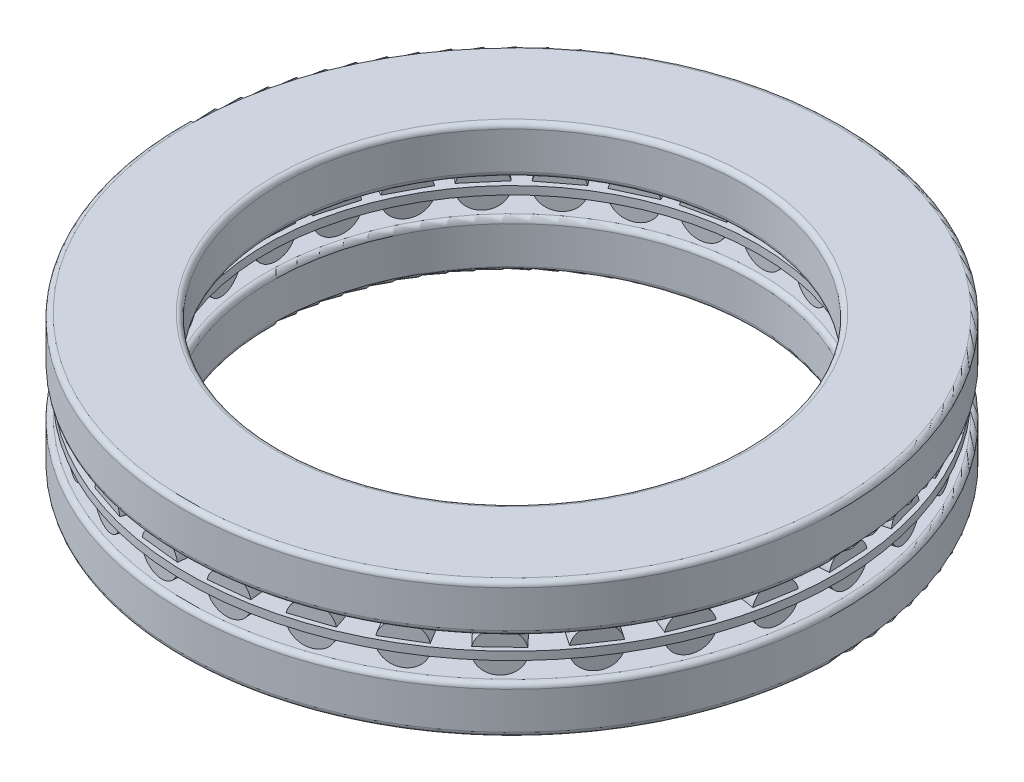
SolidWorks part; units mm, degrees
ref_plane "前视基准面" through (0, 0, 0) normal (0, 0, 1) x (1, 0, 0)
ref_plane "上视基准面" through (0, 0, 0) normal (0, 1, 0) x (1, 0, 0)
ref_plane "右视基准面" through (0, 0, 0) normal (1, 0, 0) x (0, 0, -1)
sketch "草图1" plane through (0, 0, 0) normal (1, 0, 0) x (0, 0, -1)
  line L0 (0, 40.2628) -> (0, 0) construction
  line L1 (0, 0) -> (70.6499, 0) construction
  line L2 (0, 0) -> (0, -0.6) construction
  line L3 (29.1, 2.8) -> (38.4, 2.8)
  line L4 (28.5, 2.2) -> (28.5, -2.2)
  line L5 (29.1, -2.8) -> (38.4, -2.8)
  line L6 (39, 2.2) -> (39, -2.2)
  line L7 (28.1, 13.2) -> (38.4, 13.2)
  line L8 (27.5, 12.6) -> (27.5, 8.2)
  line L9 (28.1, 7.6) -> (38.4, 7.6)
  line L10 (39, 12.6) -> (39, 8.2)
  line L11 (38.4, 5.2) -> (29.1, 5.2) construction
  line L12 (38.4, 5.68) -> (29.1, 5.68)
  line L13 (38.4, 5.68) -> (38.4, 4.72)
  line L14 (38.4, 4.72) -> (29.1, 4.72)
  line L15 (29.1, 5.68) -> (29.1, 4.72)
  arc A0 (38.4, -2.8) -> (39, -2.2) centre (38.4, -2.2) ccw
  arc A1 (38.4, 2.8) -> (39, 2.2) centre (38.4, 2.2) cw
  arc A2 (28.5, -2.2) -> (29.1, -2.8) centre (29.1, -2.2) ccw
  arc A3 (29.1, 2.8) -> (28.5, 2.2) centre (29.1, 2.2) ccw
  arc A4 (38.4, 13.2) -> (39, 12.6) centre (38.4, 12.6) cw
  arc A5 (38.4, 7.6) -> (39, 8.2) centre (38.4, 8.2) ccw
  arc A6 (27.5, 8.2) -> (28.1, 7.6) centre (28.1, 8.2) ccw
  arc A7 (28.1, 13.2) -> (27.5, 12.6) centre (28.1, 12.6) ccw
  dimension "D3" = 0.6
  dimension "D1" = 57
  dimension "T" = 16
  dimension "D" = 78
  dimension "D2" = 4.8
  dimension "(d1)" = 78
  dimension "(d)" = 55
  dimension "r" = 0.6
  dimension "D4" = 0.96
sketch "草图2" plane through (0, 0, 0) normal (1, 0, 0) x (0, 0, -1)
  line L0 (29.1, 2.8) -> (38.4, 2.8) construction
  line L1 (39, 2.2) -> (39, -2.2) construction
  line L2 (29.1, -2.8) -> (38.4, -2.8) construction
  line L3 (28.5, 2.2) -> (28.5, -2.2) construction
  line L4 (29.1, 2.8) -> (38.4, 2.8)
  line L5 (39, 2.2) -> (39, -2.2)
  line L6 (29.1, -2.8) -> (38.4, -2.8)
  line L7 (28.5, 2.2) -> (28.5, -2.2)
  line L8 (0, 0) -> (0, 14.9997) construction
  line L9 (0, 40.2628) -> (0, 0) construction
  arc A0 (39, 2.2) -> (38.4, 2.8) centre (38.4, 2.2) ccw construction
  arc A1 (38.4, -2.8) -> (39, -2.2) centre (38.4, -2.2) ccw construction
  arc A2 (28.5, -2.2) -> (29.1, -2.8) centre (29.1, -2.2) ccw construction
  arc A3 (29.1, 2.8) -> (28.5, 2.2) centre (29.1, 2.2) ccw construction
  arc A4 (39, 2.2) -> (38.4, 2.8) centre (38.4, 2.2) ccw
  arc A5 (38.4, -2.8) -> (39, -2.2) centre (38.4, -2.2) ccw
  arc A6 (28.5, -2.2) -> (29.1, -2.8) centre (29.1, -2.2) ccw
  arc A7 (29.1, 2.8) -> (28.5, 2.2) centre (29.1, 2.2) ccw
revolve "旋转1" add sketch "草图2" angle 360 mid plane about L8
sketch "草图3" plane through (0, 0, 0) normal (1, 0, 0) x (0, 0, -1)
  line L0 (28.1, 13.2) -> (38.4, 13.2) construction
  line L1 (39, 12.6) -> (39, 8.2) construction
  line L2 (28.1, 7.6) -> (38.4, 7.6) construction
  line L3 (27.5, 12.6) -> (27.5, 8.2) construction
  line L4 (28.1, 13.2) -> (38.4, 13.2)
  line L5 (39, 12.6) -> (39, 8.2)
  line L6 (28.1, 7.6) -> (38.4, 7.6)
  line L7 (27.5, 12.6) -> (27.5, 8.2)
  line L8 (0, 0) -> (0, 10.4732) construction
  line L9 (0, 40.2628) -> (0, 0) construction
  arc A0 (39, 12.6) -> (38.4, 13.2) centre (38.4, 12.6) ccw construction
  arc A1 (38.4, 7.6) -> (39, 8.2) centre (38.4, 8.2) ccw construction
  arc A2 (27.5, 8.2) -> (28.1, 7.6) centre (28.1, 8.2) ccw construction
  arc A3 (28.1, 13.2) -> (27.5, 12.6) centre (28.1, 12.6) ccw construction
  arc A4 (39, 12.6) -> (38.4, 13.2) centre (38.4, 12.6) ccw
  arc A5 (38.4, 7.6) -> (39, 8.2) centre (38.4, 8.2) ccw
  arc A6 (27.5, 8.2) -> (28.1, 7.6) centre (28.1, 8.2) ccw
  arc A7 (28.1, 13.2) -> (27.5, 12.6) centre (28.1, 12.6) ccw
revolve "旋转2" add sketch "草图3" angle 360 mid plane about L8
ref_plane "基准面1" through (0, 5.2, 0) normal (0, -1, 0) x (1, 0, 0)
sketch "草图7" plane through (0, 0, 0) normal (1, 0, 0) x (0, 0, -1)
  line L0 (38.4, 4.72) -> (29.1, 4.72) construction
  line L1 (29.1, 5.68) -> (29.1, 4.72) construction
  line L2 (38.4, 5.68) -> (29.1, 5.68) construction
  line L3 (38.4, 5.68) -> (38.4, 4.72) construction
  line L4 (38.4, 4.72) -> (29.1, 4.72)
  line L5 (29.1, 5.68) -> (29.1, 4.72)
  line L6 (38.4, 5.68) -> (29.1, 5.68)
  line L7 (38.4, 5.68) -> (38.4, 4.72)
  line L8 (0, 0) -> (0, 12.5332) construction
  line L9 (0, 40.2628) -> (0, 0) construction
revolve "旋转4" add sketch "草图7" angle 360 mid plane about L8
sketch "草图4" plane through (0, 5.2, 0) normal (0, -1, 0) x (1, 0, 0)
  line L0 (0, 0) -> (0, -19.4594) construction
  line L1 (0, 0) -> (0, -70.6499) construction
  line L3 (0, -29.7) -> (-2.4, -29.7)
  line L4 (0, -29.7) -> (0, -37.8)
  line L5 (0, -37.8) -> (-2.4, -37.8)
  line L6 (-2.4, -29.7) -> (-2.4, -37.8)
  line L7 (0, -38.4) -> (0, -29.1) construction
  dimension "D1" = 4.8
  dimension "D2" = 0.6
  dimension "D3" = 0.6
revolve "切除-旋转1" cut sketch "草图4<3>" angle 360 mid plane about L0
sketch "草图4<3>" plane through (0, 5.2, 0) normal (0, -1, 0) x (1, 0, 0) same geometry as "草图4"
pattern_circular "阵列(圆周)2" count 29 over 360 of "切除-旋转1"
revolve "旋转3" add sketch "草图4" angle 360 mid plane about L0
pattern_circular "阵列(圆周)1" count 29 over 360 of bodies 103 116
